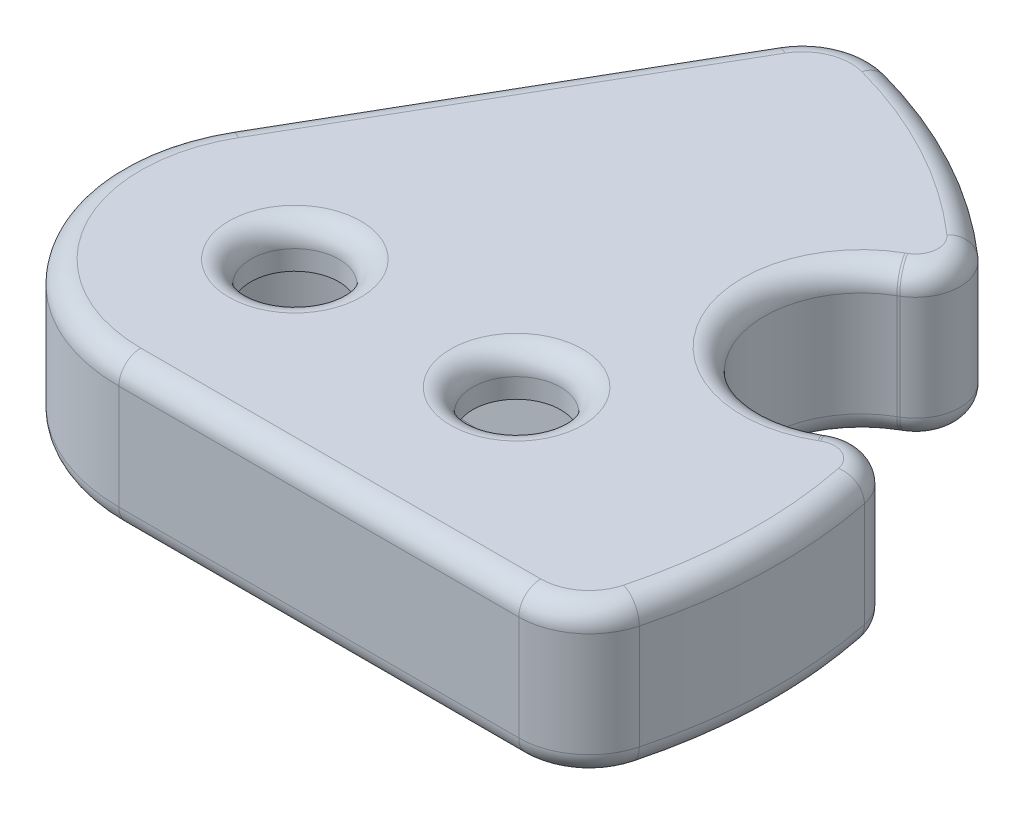
SolidWorks part; units mm, degrees
ref_plane "Front Plane" through (0, 0, 0) normal (0, 0, 1) x (1, 0, 0)
ref_plane "Top Plane" through (0, 0, 0) normal (0, 1, 0) x (1, 0, 0)
ref_plane "Right Plane" through (0, 0, 0) normal (1, 0, 0) x (0, 0, -1)
sketch "Sketch1" plane through (0, 0, 0) normal (0, 1, 0) x (1, 0, 0)
  line L0 (2.2864, 2.65) -> (14.1103, 1.997)
  line L1 (2.2864, -2.65) -> (14.1103, -1.997)
  line L2 (0, 0) -> (14, 0) construction
  line L3 (-5.4993, 3.175) -> (0, -6.35) construction
  line L5 (9.9268, 5.7313) -> (15.123, 8.7313) construction
  line L6 (11.2079, 10.5123) -> (13.0661, 11.5852)
  line L7 (14.7079, 4.4502) -> (16.5661, 5.523)
  line L8 (0, -6.35) -> (16.267, -6.35)
  line L9 (-5.4993, 3.175) -> (2.6343, 17.2627)
  line L10 (-5.4993, 3.175) -> (0, 0) construction
  line L11 (0, 0) -> (0, -6.35) construction
  circle A0 centre (0, 0) radius 3.5 construction
  arc A1 (14.1103, 1.997) -> (14.1103, -1.997) centre (14, 0) cw
  arc A2 (2.2864, 2.65) -> (2.2864, -2.65) centre (0, 0) ccw
  circle A3 centre (14, 0) radius 0.5 construction
  circle A4 centre (12, 0) radius 0.5 construction
  circle A5 centre (10, 0) radius 0.5 construction
  circle A6 centre (8, 0) radius 0.5 construction
  circle A7 centre (6, 0) radius 0.5 construction
  circle A8 centre (4, 0) radius 0.5 construction
  arc A9 (2.6343, 17.2627) -> (13.0661, 11.5852) centre (0, 0) cw
  arc A11 (11.2079, 10.5123) -> (14.7079, 4.4502) centre (12.9579, 7.4813) ccw
  arc A15 (16.267, -6.35) -> (16.5661, 5.523) centre (0, 0) ccw
  arc A16 (-5.4993, 3.175) -> (0, -6.35) centre (0, 0) ccw
  arc A18 (-17.4625, 0) -> (16.267, -6.35) centre (0, 0) ccw construction
  arc A19 (-17.4625, 0) -> (2.6343, 17.2627) centre (0, 0) cw construction
  point P4 (16, 0)
  point P6 (-3.5, 0)
  dimension "D1" = 7
  dimension "D5" = 1
  dimension "D8" = 120
  dimension "D10" = 3.5
  dimension "D4" = 2
  dimension "D11" = 6.35
  dimension "D12" = 17.4625
  dimension "D2" = 19.5
  dimension "D3" = 5.3
  dimension "D7" = 2
  dimension "D9" = 6
  dimension "D6" = 6
extrude "Boss-Extrude1" add sketch "Sketch1" along normal blind 4.5
fillet "Fillet4" radius 2.54 2 edges at (16.267, 2.25, 6.35) (2.6343, 2.25, -17.2627)
sketch "Sketch2" plane through (0, 4.5, 0) normal (0, 1, 0) x (1, 0, 0)
  line L0 (0, 0) -> (16, 0) construction
  line L5 (0, -6.35) -> (14.4279, -6.35)
  line L6 (16.5661, 5.523) -> (14.7079, 4.4502)
  line L7 (11.2079, 10.5123) -> (13.0661, 11.5852)
  line L10 (16.5661, 5.523) -> (14.7079, 4.4502)
  line L11 (11.2079, 10.5123) -> (13.0661, 11.5852)
  line L12 (0, -6.35) -> (14.4279, -6.35)
  line L13 (1.7147, 15.6699) -> (-5.4993, 3.175)
  line L14 (1.7147, 15.6699) -> (-5.4993, 3.175)
  circle A0 centre (0, 0) radius 1.5875
  circle A1 centre (8, 0) radius 1.5875
  arc A2 (14.1103, -1.997) -> (14.1103, 1.997) centre (14, 0) ccw construction
  arc A7 (13.0661, 11.5852) -> (4.5807, 16.851) centre (0, 0) ccw
  arc A8 (13.0661, 11.5852) -> (4.5807, 16.851) centre (0, 0) ccw
  arc A9 (-5.4993, 3.175) -> (0, -6.35) centre (0, 0) ccw
  arc A11 (16.8837, -4.4585) -> (16.5661, 5.523) centre (0, 0) ccw
  arc A13 (11.2079, 10.5123) -> (14.7079, 4.4502) centre (12.9579, 7.4813) ccw
  arc A15 (14.4279, -6.35) -> (16.8837, -4.4585) centre (14.4279, -3.81) ccw
  arc A19 (16.8837, -4.4585) -> (16.5661, 5.523) centre (0, 0) ccw
  arc A21 (11.2079, 10.5123) -> (14.7079, 4.4502) centre (12.9579, 7.4813) ccw
  arc A22 (14.4279, -6.35) -> (16.8837, -4.4585) centre (14.4279, -3.81) ccw
  arc A23 (4.5807, 16.851) -> (1.7147, 15.6699) centre (3.9144, 14.3999) ccw
  arc A24 (4.5807, 16.851) -> (1.7147, 15.6699) centre (3.9144, 14.3999) ccw
  arc A25 (-5.4993, 3.175) -> (0, -6.35) centre (0, 0) ccw
  point P15 (8, 0)
  dimension "D2" = 3.175
  dimension "D3" = 3.175
  dimension "D1" = 0
extrude "Boss-Extrude2" add sketch "Sketch2" along normal offset from surface (1.5 mm away) 6 up to face at (8.3109, 0, -4.7983)
sketch "Sketch3" plane through (0, 0, 0) normal (0, -1, 0) x (1, 0, 0)
  line L4 (13.0661, -11.5852) -> (11.2079, -10.5123)
  line L5 (14.7079, -4.4502) -> (16.5661, -5.523)
  line L6 (-5.4993, -3.175) -> (1.7147, -15.6699)
  line L7 (-5.4993, -3.175) -> (1.7147, -15.6699)
  line L8 (13.0661, -11.5852) -> (11.2079, -10.5123)
  line L9 (14.7079, -4.4502) -> (16.5661, -5.523)
  line L10 (14.4279, 6.35) -> (0, 6.35)
  line L11 (14.4279, 6.35) -> (0, 6.35)
  arc A4 (16.5661, -5.523) -> (16.8837, 4.4585) centre (0, 0) ccw
  arc A5 (16.5661, -5.523) -> (16.8837, 4.4585) centre (0, 0) ccw
  arc A6 (0, 6.35) -> (-5.4993, -3.175) centre (0, 0) ccw
  arc A7 (4.5807, -16.851) -> (13.0661, -11.5852) centre (0, 0) ccw
  arc A8 (14.7079, -4.4502) -> (11.2079, -10.5123) centre (12.9579, -7.4813) ccw
  arc A13 (4.5807, -16.851) -> (13.0661, -11.5852) centre (0, 0) ccw
  arc A14 (14.7079, -4.4502) -> (11.2079, -10.5123) centre (12.9579, -7.4813) ccw
  arc A15 (16.8837, 4.4585) -> (14.4279, 6.35) centre (14.4279, 3.81) ccw
  arc A16 (16.8837, 4.4585) -> (14.4279, 6.35) centre (14.4279, 3.81) ccw
  arc A17 (1.7147, -15.6699) -> (4.5807, -16.851) centre (3.9144, -14.3999) ccw
  arc A18 (1.7147, -15.6699) -> (4.5807, -16.851) centre (3.9144, -14.3999) ccw
  arc A19 (0, 6.35) -> (-5.4993, -3.175) centre (0, 0) ccw
  dimension "D1" = 0
extrude "Cut-Extrude1" cut sketch "Sketch3" against normal blind 0.635
fillet "Fillet1" radius 1.5875 2 edges at (16.5661, 3.3175, -5.523) (13.0661, 3.3175, -11.5852)
fillet "Fillet2" radius 0.7937 16 edges at (9.9268, 0.635, -5.7313) (11.2405, 0.635, -10.5311) (12.0591, 0.635, -11.7684) (8.2675, 0.635, -15.3814) (17.4544, 0.635, 0.5308) (16.2212, 0.635, -4.5593) (14.7405, 0.635, -4.469) (-3.5, 0.635, 0) (8.1983, 0.635, -2.3235) (16, 0.635, 0) (8.1983, 0.635, 2.3235) (-1.8923, 0.635, -9.4225) (7.214, 0.635, 6.35) (2.9466, 0.635, -16.7484) (15.9778, 0.635, 5.8223) (-5.4993, 0.635, 3.175)
fillet "Fillet3" radius 0.7937 14 edges at (8.2675, 6, -15.3814) (12.0591, 6, -11.7684) (11.2405, 6, -10.5311) (9.9268, 6, -5.7313) (14.7405, 6, -4.469) (16.2212, 6, -4.5593) (17.4544, 6, 0.5308) (0, 6, 1.5875) (8, 6, 1.5875) (7.214, 6, 6.35) (-5.4993, 6, 3.175) (-1.8923, 6, -9.4225) (15.9778, 6, 5.8223) (2.9466, 6, -16.7484)
ref_plane "Midplane " through (0, 0, 0) normal (-0.5, 0, -0.866) x (-0.866, 0, 0.5)
